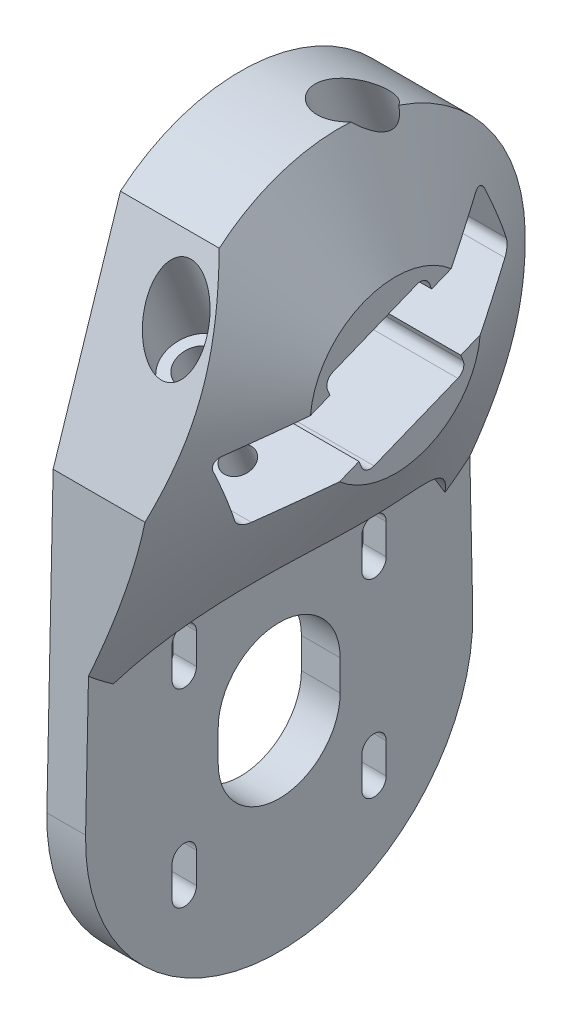
SolidWorks part; units mm, degrees
ref_plane "Front Plane" through (0, 0, 0) normal (0, 0, 1) x (1, 0, 0)
ref_plane "Top Plane" through (0, 0, 0) normal (0, 1, 0) x (1, 0, 0)
ref_plane "Right Plane" through (0, 0, 0) normal (1, 0, 0) x (0, 0, -1)
sketch "Sketch1" plane through (0, 0, 0) normal (1, 0, 0) x (0, 0, -1)
  line L0 (4.9732, 11.7161) -> (-11.7161, 4.9732)
  line L1 (4.9732, 11.7161) -> (11.7161, -4.9732)
  line L2 (-11.7161, 4.9732) -> (-4.9732, -11.7161)
  line L3 (11.7161, -4.9732) -> (-4.9732, -11.7161)
  line L4 (4.9732, 11.7161) -> (-4.9732, -11.7161) construction
  line L5 (-11.7161, 4.9732) -> (11.7161, -4.9732) construction
  line L6 (0, 0) -> (0, -57.15) construction
  line L7 (-30.4731, 0.6489) -> (-31.7428, -58.974)
  line L8 (31.7428, -58.974) -> (30.4731, 0.6489)
  line L9 (0, -57.15) -> (0, -103.9417) construction
  arc A0 (30.4731, 0.6489) -> (-30.4731, 0.6489) centre (0, 0) ccw
  arc A1 (-31.7428, -58.974) -> (31.7428, -58.974) centre (0, -59.65) ccw
  dimension "D1" = 2.5
  dimension "D2" = 30.48
  dimension "D6" = 57.15
  dimension "D7" = 31.75
  dimension "D8" = 0
  dimension "D3" = 18
  dimension "D4" = 18
  dimension "D5" = 22
extrude "Boss-Extrude1" add sketch "Sketch1" along normal blind 6.35 contours L7 A0 L1 L3 L2 L0 region at (0, -32.4026, 0)
sketch "Sketch19" plane through (6.35, 0, 0) normal (1, 0, 0) x (0, 0, -1)
  line L0 (0, -59.65) -> (0, -54.65)
  line L1 (0, -54.65) -> (15.5563, -39.0937) construction
  line L2 (15.5563, -44.0937) -> (15.5563, -39.0937) construction
  line L3 (13.5563, -44.0937) -> (13.5563, -39.0937)
  line L4 (17.5563, -44.0937) -> (17.5563, -39.0937)
  line L5 (-10, -59.65) -> (-10, -54.65)
  line L6 (10, -59.65) -> (10, -54.65)
  line L7 (0, -57.15) -> (7.4061, -57.15) construction
  line L8 (15.5563, -44.0937) -> (0, -59.65) construction
  line L9 (17.5563, -70.2063) -> (17.5563, -75.2063)
  line L10 (13.5563, -70.2063) -> (13.5563, -75.2063)
  line L11 (-17.5563, -44.0937) -> (-17.5563, -39.0937)
  line L12 (-13.5563, -44.0937) -> (-13.5563, -39.0937)
  line L13 (-13.5563, -70.2063) -> (-13.5563, -75.2063)
  line L14 (-17.5563, -70.2063) -> (-17.5563, -75.2063)
  line L15 (-15.5563, -44.0937) -> (0, -59.65) construction
  line L16 (0, -59.65) -> (-15.5563, -75.2063) construction
  line L17 (0, -59.65) -> (15.5563, -75.2063) construction
  arc A0 (-31.7428, -58.974) -> (31.7428, -58.974) centre (0, -59.65) ccw construction
  arc A1 (-31.7428, -58.974) -> (31.7428, -58.974) centre (0, -59.65) ccw
  arc A2 (-10, -59.65) -> (10, -59.65) centre (0, -59.65) ccw
  arc A3 (17.5563, -75.2063) -> (13.5563, -75.2063) centre (15.5563, -75.2063) cw
  arc A4 (13.5563, -70.2063) -> (17.5563, -70.2063) centre (15.5563, -70.2063) cw
  arc A6 (17.5563, -39.0937) -> (13.5563, -39.0937) centre (15.5563, -39.0937) ccw
  arc A7 (13.5563, -44.0937) -> (17.5563, -44.0937) centre (15.5563, -44.0937) ccw
  arc A8 (-17.5563, -39.0937) -> (-13.5563, -39.0937) centre (-15.5563, -39.0937) cw
  arc A9 (10, -54.65) -> (-10, -54.65) centre (0, -54.65) ccw
  arc A10 (-13.5563, -44.0937) -> (-17.5563, -44.0937) centre (-15.5563, -44.0937) cw
  arc A11 (-13.5563, -70.2063) -> (-17.5563, -70.2063) centre (-15.5563, -70.2063) ccw
  arc A13 (-17.5563, -75.2063) -> (-13.5563, -75.2063) centre (-15.5563, -75.2063) ccw
  point P8 (0, -57.15)
  dimension "D1" = 135
  dimension "D3" = 22
  dimension "D5" = 4
  dimension "D6" = 5
  dimension "D4" = 4
  dimension "D8" = 0
  dimension "D2" = 5
  dimension "D7" = 45
extrude "Cut-Extrude18" cut sketch "Sketch19" against normal blind 10 contours L6 A9 L5 A2 | A10 L12 A8 L11 | L14 A13 L13 A11 | A4 L10 A3 L9 | L4 A6 L3 A7 region at (6.35, -57.15, 9.6798) region at (6.35, -72.7063, -15.5563) region at (6.35, -41.5937, 15.5563) region at (6.35, -72.7063, 15.5563)
sketch "Sketch20" plane through (6.35, 0, 0) normal (1, 0, 0) x (0, 0, -1)
  circle A0 centre (0, 0) radius 57.15
  arc A1 (-31.7428, -58.974) -> (31.7428, -58.974) centre (0, -59.65) ccw construction
  point P3 (0, -91.4)
extrude "Boss-Extrude5" add sketch "Sketch20" along normal blind 19.05
sketch "Sketch21" plane through (0, 0, 0) normal (-1, 0, 0) x (0, 0, 1)
  line L0 (-24.6312, 3.1029) -> (-10.7234, -2.5162)
  line L1 (11.7161, 4.9732) -> (4.9732, -11.7161) construction
  line L2 (3.3715, 8.3447) -> (-3.3715, -8.3447) construction
  line L3 (-4.9732, 11.7161) -> (-11.7161, -4.9732) construction
  line L4 (-4.9732, 11.7161) -> (11.7161, 4.9732) construction
  line L5 (11.7161, 4.9732) -> (10.7234, 2.5162)
  line L6 (-11.7161, -4.9732) -> (4.9732, -11.7161) construction
  line L7 (-4.9732, 11.7161) -> (-5.9659, 9.2591)
  line L8 (-4.9732, 11.7161) -> (11.7161, 4.9732)
  line L9 (-22.2524, 8.9906) -> (-14.2742, 5.7671) construction
  line L10 (19.8737, -14.8782) -> (5.9659, -9.2591)
  line L11 (19.8737, -14.8782) -> (24.6312, -3.1029)
  line L12 (-24.6312, 3.1029) -> (-19.8737, 14.8782)
  line L13 (24.6312, -3.1029) -> (10.7234, 2.5162)
  line L14 (-11.7161, -4.9732) -> (4.9732, -11.7161)
  line L16 (4.9732, -11.7161) -> (5.9659, -9.2591)
  line L17 (-11.7161, -4.9732) -> (-10.7234, -2.5162)
  line L18 (11.7161, 4.9732) -> (-4.9732, 11.7161)
  line L21 (-10.7234, -2.5162) -> (-11.7161, -4.9732)
  line L24 (-10.7234, -2.5162) -> (-24.6312, 3.1029)
  line L27 (-5.9659, 9.2591) -> (-4.9732, 11.7161)
  line L29 (-5.9659, 9.2591) -> (-19.8737, 14.8782)
  line L30 (5.9659, -9.2591) -> (4.9732, -11.7161)
  line L31 (10.7234, 2.5162) -> (11.7161, 4.9732)
  point P4 (-22.2524, 8.9906)
  line M13 (-11.7161, -4.9732) -> (-4.9732, 11.7161)
  line M14 (-4.9732, 11.7161) -> (11.7161, 4.9732)
  line M15 (11.7161, 4.9732) -> (4.9732, -11.7161)
  line M16 (4.9732, -11.7161) -> (-11.7161, -4.9732)
  dimension "D1" = 15
  dimension "D2" = 12.7
  dimension "D3" = 15
extrude "Cut-Extrude14" cut sketch "Sketch21" against normal through all contours L29 L12 L0 M13 | M13 M16 M15 M14 | L11 L13 L10 M15 region at (0, 6.181, -15.2985) region at (0, 0, 0) region at (0, -6.181, 15.2985)
sketch "Sketch22" plane through (0, 5.8876, 2.3788) normal (0, -0.9272, -0.3746) x (1, 0, 0)
  line L0 (25.4, 9) -> (0, 9) construction
  line L2 (0, 28.0111) -> (0, -30.48) construction
  circle A0 centre (12.5, 16.5) radius 3.175
  dimension "D2" = 12.5
  dimension "D3" = 6.35
  dimension "D1" = 7.5
extrude "Cut-Extrude15" cut sketch "Sketch22" against normal through all
ref_plane "Plane1" through (0, 10.5977, 4.2818) normal (0, -0.9272, -0.3746) x (1, 0, 0)
sketch "Sketch24" plane through (0, 10.5977, 4.2818) normal (0, -0.9272, -0.3746) x (1, 0, 0)
  circle A0 centre (12.5, 16.5) radius 5
  dimension "D1" = 10
extrude "Cut-Extrude16" cut sketch "Sketch24" against normal through all
sketch "Sketch25" plane through (0, -5.8876, -2.3788) normal (0, 0.9272, 0.3746) x (-1, 0, 0)
  circle A0 centre (-12.5, 16.5) radius 3.175 construction
  circle A1 centre (-12.5, 16.5) radius 3.175
  circle A2 centre (-12.5, 16.5) radius 2.3813
  dimension "D1" = 0.7937
extrude "Cut-Extrude17" cut sketch "Sketch25" against normal blind 10 contours A2 region at (12.5, -12.0686, 12.9198)
ref_plane "Plane2" through (0, 0, 0) normal (0, 0.3746, -0.9272) x (-1, 0, 0)
mirror "Mirror1" about plane through (0, 0, 0) normal (0, 0.3746, -0.9272) of "Cut-Extrude17", "Cut-Extrude15", "Cut-Extrude16"
mirror "Mirror2" about plane through (0, 0, 0) normal (1, 0, 0) of bodies 124 126
delete or keep bodies "Body-Delete/Keep 1" type delete bodies bodies 127
chamfer "Chamfer2" distance 2.5 angle 45 8 edges at (0, -46.0937, 15.5563) (0, -41.5937, 13.5563) (0, -37.0937, 15.5563) (0, -41.5937, 17.5563) (0, -46.0937, -15.5563) (0, -41.5937, -17.5563) (0, -41.5937, -13.5563) (0, -37.0937, -15.5563)
sketch "Sketch26" plane through (0, 0, 0) normal (-1, 0, 0) x (0, 0, 1)
  line L0 (11.4538, -58.2291) -> (27.0119, -8.4408)
  line L1 (0, 0) -> (0, -54.65) construction
  circle A0 centre (0, -54.65) radius 12
  circle A1 centre (0, 0) radius 28.3
  dimension "D1" = 24
  dimension "D2" = 56.6
fillet "Fillet1" radius 1.5875 8 edges at (12.7, -4.9732, -11.7161) (12.7, 3.1029, -24.6312) (12.7, 11.7161, -4.9732) (12.7, 14.8782, -19.8737) (12.7, -3.1029, 24.6312) (12.7, 4.9732, 11.7161) (12.7, -11.7161, 4.9732) (12.7, -14.8782, 19.8737)
sketch "Sketch28" plane through (6.35, 0, 0) normal (1, 0, 0) x (0, 0, -1)
  arc A0 (-10, -54.65) -> (10, -54.65) centre (0, -54.65) ccw construction
  arc A1 (-10, -54.65) -> (10, -54.65) centre (0, -54.65) ccw
  circle A3 centre (0, -54.65) radius 31
  dimension "D1" = 62
extrude "Cut-Extrude19" cut sketch "Sketch28" along normal through all contours A3
sketch "Sketch29" plane through (25.4, 0, 0) normal (1, 0, 0) x (0, 0, -1)
  arc A1 (30.4731, 0.6489) -> (-30.4731, 0.6489) centre (0, 0) ccw construction
  arc A2 (30.4731, 0.6489) -> (-30.4731, 0.6489) centre (0, 0) ccw
  circle A3 centre (0, 0) radius 13.97
sketch "Sketch30" plane through (6.35, 0, 0) normal (1, 0, 0) x (0, 0, -1)
  circle A0 centre (0, 0) radius 57.15
sketch "Sketch31" plane through (0, 0, 0) normal (0, 1, 0) x (1, 0, 0)
  line L1 (25.4, -13.97) -> (25.4, 14.03)
  line L3 (6.35, -48.173) -> (4.8643, 48.1615)
  line L4 (25.4, -13.97) -> (6.35, -48.173)
  line L5 (6.35, -48.173) -> (6.35, -58.97)
  line L6 (6.35, -58.97) -> (25.4, -58.97)
  line L7 (25.4, -58.97) -> (25.4, -13.97)
  line L8 (25.4, 0) -> (0, 0) construction
  dimension "D1" = 45
  dimension "D2" = 30
  dimension "D3" = 28
  dimension "D4" = 28
revolve "Cut-Revolve1" cut sketch "Sketch31" angle 360 about L8 region at (17.8212, 0, 43.2736)
sketch "Sketch32" plane through (6.35, 0, 0) normal (-1, 0, 0) x (0, 0, 1)
  line L0 (30.4731, 0.6489) -> (31.7428, -58.974) construction
  line L1 (-31.7428, -58.974) -> (-30.4731, 0.6489) construction
  line L2 (30.4731, 0.6489) -> (31.7428, -58.974)
  line L3 (-31.7428, -58.974) -> (-30.4731, 0.6489)
  arc A0 (30.4731, 0.6489) -> (-30.4731, 0.6489) centre (0, 0) ccw construction
  arc A1 (30.4731, 0.6489) -> (-30.4731, 0.6489) centre (0, 0) ccw
  circle A2 centre (0, 0) radius 57.15 construction
  circle A3 centre (0, 0) radius 57.15
  arc M2 (31.2673, -36.6468) -> (-31.2673, -36.6468) centre (0, 0) ccw
  line M3 (-31.2673, -36.6468) -> (-30.4731, 0.6489)
  arc M4 (-30.4731, 0.6489) -> (30.4731, 0.6489) centre (0, 0) cw
  line M5 (30.4731, 0.6489) -> (31.2673, -36.6468)
extrude "Cut-Extrude20" cut sketch "Sketch32" against normal through all contours M5 M2 M3 M4 region at (6.35, 31.7636, 0)
sketch "Sketch33" plane through (0, 0, 0) normal (-1, 0, 0) x (0, 0, 1)
  line L0 (30.4731, 0.6489) -> (31.7428, -58.974) construction
  line L1 (30.4731, 0.6489) -> (31.7428, -58.974)
  line L2 (30.7146, -10.6896) -> (19.6783, 23.2765)
  line L3 (23.1593, -2.5083) -> (10.7234, 2.5162) construction
  arc A0 (30.4731, 0.6489) -> (-30.4731, 0.6489) centre (0, 0) ccw construction
  arc A1 (30.4731, 0.6489) -> (-30.4731, 0.6489) centre (0, 0) ccw
  arc M35 (30.4731, 0.6489) -> (-30.4731, 0.6489) centre (0, 0) ccw
  dimension "D1" = 50
  dimension "D2" = 25.908
extrude "Cut-Extrude21" cut sketch "Sketch33" against normal through all contours L2 L1 M35 region at (0, 7.9201, 26.5605)
sketch "Sketch34" plane through (25.4, 0, 0) normal (1, 0, 0) x (0, 0, -1)
  line L0 (-9.1586, -10.549) -> (-18.4018, -14.2835) construction
  line L1 (-9.1586, -10.549) -> (-18.4018, -14.2835)
  arc A0 (-9.1586, -10.549) -> (13.9161, -1.2262) centre (0, 0) ccw construction
  dimension "D1" = 23.2947
sketch "Sketch35" plane through (0, -5.8876, -2.3788) normal (0, 0.9272, 0.3746) x (-1, 0, 0)
  line L0 (0, 22.4125) -> (0, 9) construction
  line L4 (-19.553, 24) -> (0, 24) construction
  line L5 (-19.553, 24) -> (0, 24)
  spline S0 degree 3 poles (-713.6017, 742.9697) (105.8121, 182.6367) (25.0413, 108.9315) (-55.3928, -44.7506) (-73.6374, -114.0098) (766.847, -597.7234) knots -27.053447 -27.053447 -27.053447 -27.053447 0.5 0.5 19.2326 19.2326 19.2326 19.2326 only from (-20.2064, 22.4125) to (-25.4, 12.4434) construction
  spline S1 degree 3 poles (-20.2064, 22.4125) (-21.0914, 20.7611) (-21.9711, 19.1068) (-23.7089, 15.7865) (-24.5676, 14.1214) (-25.4, 12.4434) knots 0 0 0 0 0.5 0.5 1 1 1 1
  dimension "D1" = 5.1936
  dimension "D2" = 20.2064
  dimension "D3" = 19.553
equation "\".75i\"=14.27"
